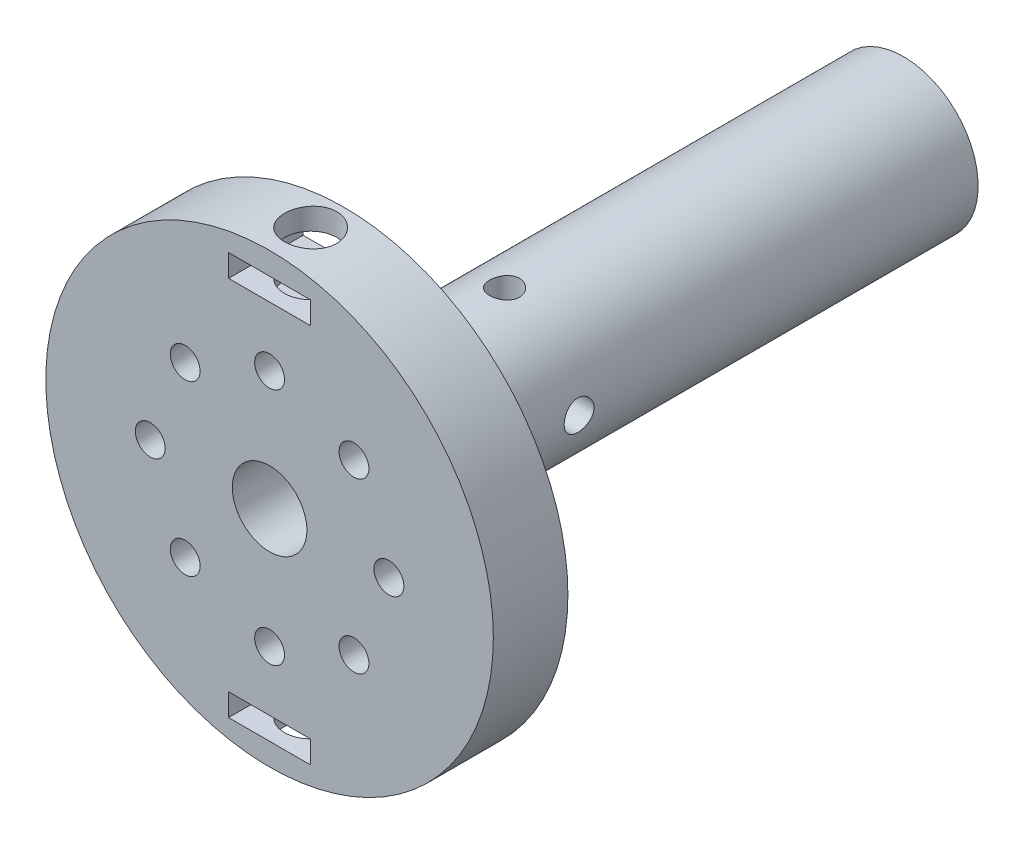
SolidWorks part; units mm, degrees
ref_plane "Front Plane" through (0, 0, 0) normal (0, 0, 1) x (1, 0, 0)
ref_plane "Top Plane" through (0, 0, 0) normal (0, 1, 0) x (1, 0, 0)
ref_plane "Right Plane" through (0, 0, 0) normal (1, 0, 0) x (0, 0, -1)
sketch "Sketch1" plane through (0, 0, 0) normal (0, 0, 1) x (1, 0, 0)
  circle A0 centre (0, 0) radius 30
  dimension "D1" = 60
extrude "Boss-Extrude1" add sketch "Sketch1" along normal blind 10
sketch "Sketch2" plane through (0, 0, 0) normal (0, 0, -1) x (-1, 0, 0)
  circle A0 centre (0, 0) radius 10
  dimension "D1" = 20
extrude "Boss-Extrude2" add sketch "Sketch2" along normal blind 75
extrude "Boss-Extrude3" add sketch "Sketch2<2>" along normal blind 20
sketch "Sketch2<2>" plane through (0, 0, 0) normal (0, 0, -1) x (-1, 0, 0) same geometry as "Sketch2"
sketch "Sketch5" plane through (0, 0, -75) normal (0, 0, -1) x (-1, 0, 0)
  circle A0 centre (0, 0) radius 5
  dimension "D1" = 10
extrude "Cut-Extrude1" cut sketch "Sketch5" against normal through all
sketch "Sketch6" plane through (0, 0, 0) normal (0, 1, 0) x (1, 0, 0)
  line L1 (30, 0) -> (-30, 0) construction
  circle A0 centre (0, 21.5) radius 2
  dimension "D1" = 4
  dimension "D2" = 21.5
extrude "Cut-Extrude2" cut sketch "Sketch6" against normal through all both and the other way through all
pattern_circular "CirPattern1" count 2 over 90 about axis through (0, 0, -75) along (0, 0, 1) of "Cut-Extrude2"
sketch "Sketch7" plane through (0, 0, 10) normal (0, 0, 1) x (1, 0, 0)
  circle A0 centre (0, 16) radius 2
  circle A1 centre (11.3137, 11.3137) radius 2
  circle A2 centre (16, 0) radius 2
  circle A3 centre (11.3137, -11.3137) radius 2
  circle A4 centre (0, -16) radius 2
  circle A5 centre (-11.3137, -11.3137) radius 2
  circle A6 centre (-16, 0) radius 2
  circle A7 centre (-11.3137, 11.3137) radius 2
  point P20 (0, 0)
  dimension "D1" = 4
  dimension "D2" = 16
  dimension "D3" = 8
extrude "Cut-Extrude3" cut sketch "Sketch7" against normal through all and the other way through all
sketch "Sketch9" plane through (0, 0, 0) normal (0, 0, -1) x (-1, 0, 0)
  line L0 (0, 0) -> (0, 30) construction
  line L3 (-5.5, 24) -> (5.5, 24)
  line L4 (-5.5, 24) -> (-5.5, 27)
  line L5 (-5.5, 27) -> (5.5, 27)
  line L6 (5.5, 24) -> (5.5, 27)
  line L7 (-5.5, 24) -> (5.5, 27) construction
  line L8 (-5.5, 27) -> (5.5, 24) construction
  circle A0 centre (0, 0) radius 30 construction
  point P6 (0, 25.5)
  dimension "D1" = 11
  dimension "D2" = 3
  dimension "D3" = 24
extrude "Cut-Extrude5" cut sketch "Sketch9" against normal blind 10
mirror "Mirror1" about plane through (0, 0, 0) normal (0, 1, 0) of "Cut-Extrude5"
ref_plane "Plane1" through (0, -30, 0) normal (0, -1, 0) x (-1, 0, 0)
sketch "Sketch10" plane through (0, -30, 0) normal (0, -1, 0) x (-1, 0, 0)
  line L1 (0, -1) -> (1.1394, -1) construction
  line L2 (30, 0) -> (-30, 0) construction
  circle A0 centre (0, -4.5) radius 3.5
  dimension "D1" = 7
  dimension "D2" = 1
  dimension "D3" = 3.5
extrude "Cut-Extrude6" cut sketch "Sketch10" against normal blind 8
mirror "Mirror2" about plane through (0, 0, 0) normal (0, 1, 0) of "Cut-Extrude6"
sketch "Sketch15" plane through (0, 0, 0) normal (0, 1, 0) x (1, 0, 0)
  line L0 (-30.0139, 50) -> (35.3147, 50) construction
  line L1 (10, 75) -> (-10, 75) construction
  dimension "D1" = 25
ref_plane "Plane3" through (0, 0, -50) normal (0, 0, -1) x (-1, 0, 0)
sketch "Sketch17" plane through (0, 0, -50) normal (0, 0, -1) x (-1, 0, 0)
  circle A0 centre (0, 0) radius 7.3556
extrude "Boss-Extrude4" add sketch "Sketch17" along normal blind 25
sketch "Sketch18" plane through (0, 0, -75) normal (0, 0, -1) x (-1, 0, 0)
  circle A0 centre (0, 0) radius 3
  dimension "D1" = 6
extrude "Cut-Extrude7" cut sketch "Sketch18" against normal blind 15
sketch "Sketch19" plane through (0, 0, -60) normal (0, 0, -1) x (-1, 0, 0)
  line L0 (0, 0) -> (0, 2.5) construction
  line L1 (1.6583, 2.5) -> (-1.6583, 2.5)
  arc A0 (1.6583, 2.5) -> (-1.6583, 2.5) centre (0, 0) ccw
  dimension "D1" = 2.5
extrude "Boss-Extrude5" add sketch "Sketch19" along normal blind 10
